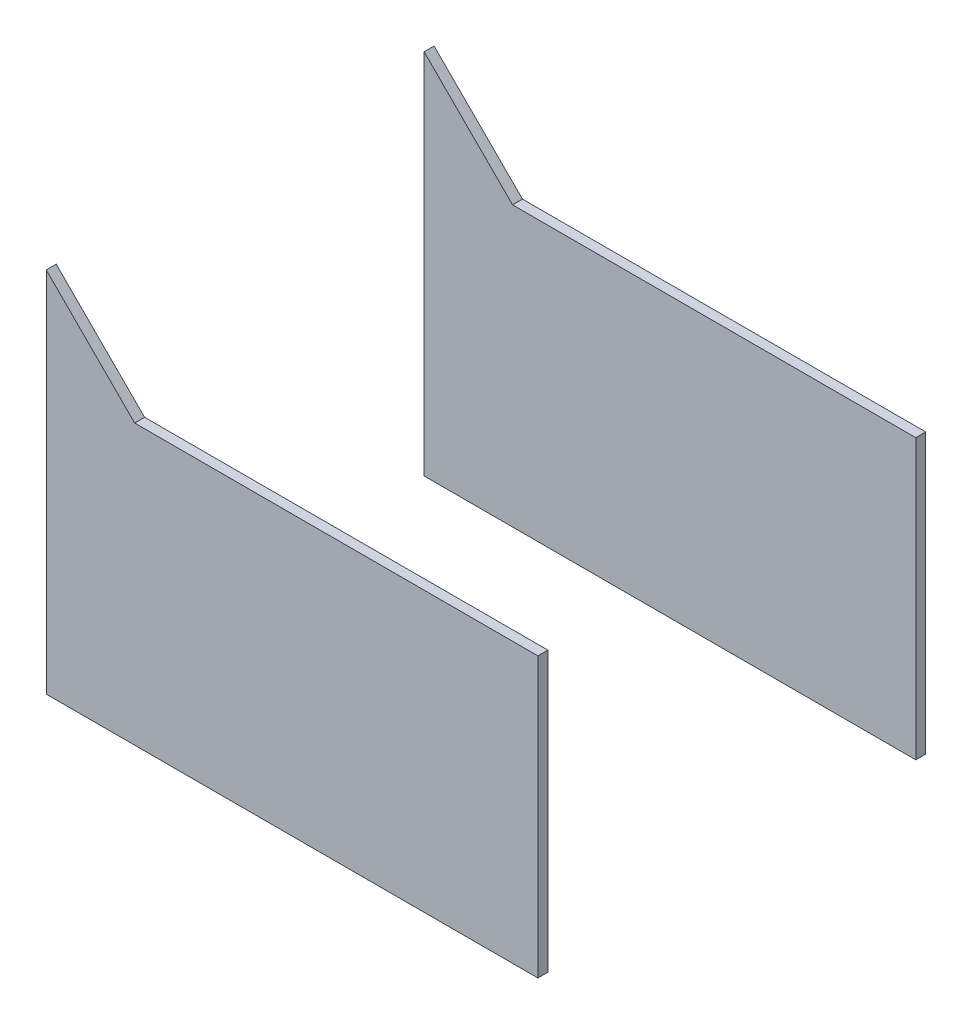
SolidWorks part; units mm, degrees
ref_plane "Front Plane" through (0, 0, 0) normal (0, 0, 1) x (1, 0, 0)
ref_plane "Top Plane" through (0, 0, 0) normal (0, 1, 0) x (1, 0, 0)
ref_plane "Right Plane" through (0, 0, 0) normal (1, 0, 0) x (0, 0, -1)
sketch "Sketch1" plane through (0, 0, 0) normal (0, 0, 1) x (1, 0, 0)
  line L0 (-247.2026, 184.7284) -> (-247.2026, -184.7284)
  line L1 (-247.2026, 184.7284) -> (-158.2986, 95.8243)
  line L2 (-158.2986, 95.8243) -> (247.2026, 95.8243)
  line L3 (247.2026, 95.8243) -> (247.2026, -184.7284)
  line L4 (247.2026, -184.7284) -> (-247.2026, -184.7284)
extrude "Boss-Extrude1" add sketch "Sketch1" along normal blind 10 from offset 185 contours L2 L3 L4 L0 L1
extrude "Boss-Extrude2" add sketch "Sketch1<3>" against normal blind 10 from offset 185 separate body offset against normal yes
sketch "Sketch1<3>" plane through (0, 0, 0) normal (0, 0, 1) x (1, 0, 0) same geometry as "Sketch1"
